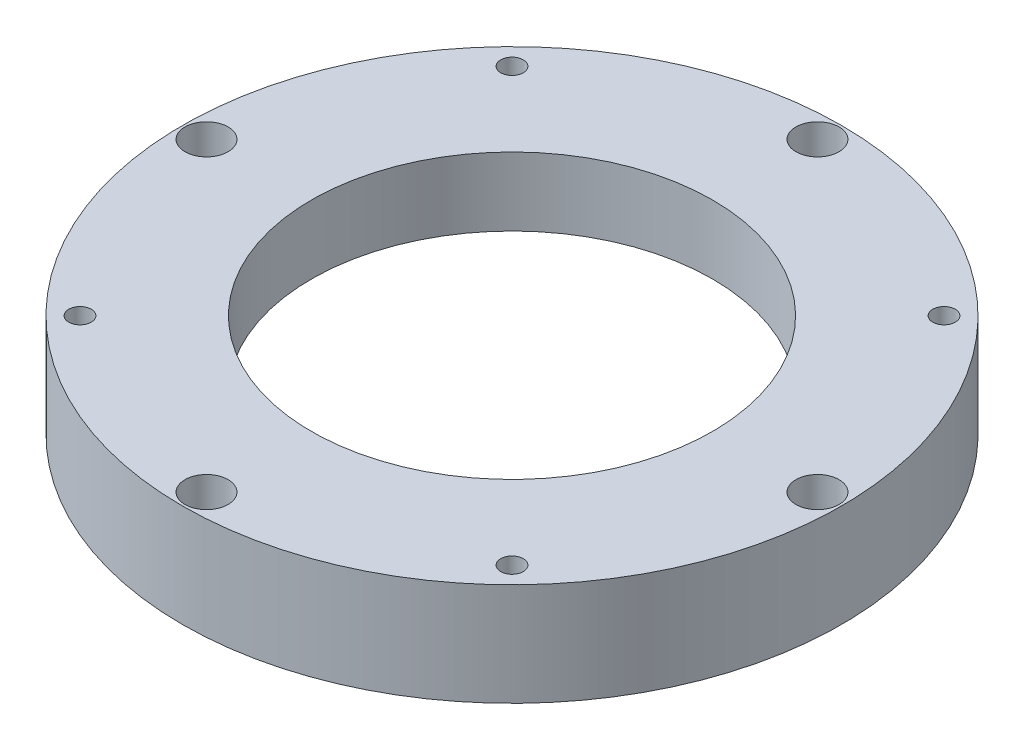
SolidWorks part; units mm, degrees
ref_plane "Front Plane" through (0, 0, 0) normal (0, 0, 1) x (1, 0, 0)
ref_plane "Top Plane" through (0, 0, 0) normal (0, 1, 0) x (1, 0, 0)
ref_plane "Right Plane" through (0, 0, 0) normal (1, 0, 0) x (0, 0, -1)
sketch "Sketch1" plane through (0, 0, 0) normal (0, 1, 0) x (1, 0, 0)
  line L0 (0, 0) -> (42.5, 0) construction
  circle A0 centre (0, 0) radius 45.85
  circle A1 centre (0, 0) radius 27.9
  circle A2 centre (42.5, 0) radius 1.5635
  circle A3 centre (30.052, -30.052) radius 1.5635
  circle A4 centre (0, -42.5) radius 1.5635
  circle A5 centre (0, 0) radius 40
  circle A6 centre (-30.052, -30.052) radius 1.5635
  circle A7 centre (-42.5, 0) radius 1.5635
  circle A8 centre (-30.052, 30.052) radius 1.5635
  circle A9 centre (0, 42.5) radius 1.5635
  circle A10 centre (30.052, 30.052) radius 1.5635
  point P13 (0, 0)
  dimension "D1" = 91.7
  dimension "D2" = 55.8
  dimension "D4" = 3.127
  dimension "D6" = 80
  dimension "D3" = 42.5
  dimension "D5" = 8
extrude "Boss-Extrude1" add sketch "Sketch1" against normal blind 4.7625 contours A0 A5 A2 A4 A3 region at (-44.5532, 0, 0)
extrude "Boss-Extrude2" add sketch "Sketch1<4>" along normal blind 4.7625 contours A1 A5 | A0 A5 A2 A4 A3 region at (-44.5532, 0, 0) region at (-38.8686, 0, 0)
sketch "Sketch1<4>" plane through (0, 0, 0) normal (0, 1, 0) x (1, 0, 0) same geometry as "Sketch1"
sketch "Sketch4" plane through (0, 4.7625, 0) normal (0, 1, 0) x (1, 0, 0)
  line L0 (28.4932, -27.352) -> (26.9343, -30.052)
  line L7 (30.052, 33.1697) -> (27.352, 31.6109)
  line L8 (27.352, 31.6109) -> (27.352, 28.4932)
  line L9 (27.352, 28.4932) -> (30.052, 26.9343)
  line L10 (30.052, 26.9343) -> (32.752, 28.4932)
  line L11 (32.752, 28.4932) -> (32.752, 31.6109)
  line L12 (32.752, 31.6109) -> (30.052, 33.1697)
  line L13 (31.6109, -27.352) -> (28.4932, -27.352)
  line L14 (33.1697, -30.052) -> (31.6109, -27.352)
  line L15 (31.6109, -32.752) -> (33.1697, -30.052)
  line L16 (28.4932, -32.752) -> (31.6109, -32.752)
  line L17 (26.9343, -30.052) -> (28.4932, -32.752)
  line L18 (-27.352, -28.4932) -> (-30.052, -26.9343)
  line L19 (-27.352, -31.6109) -> (-27.352, -28.4932)
  line L20 (-30.052, -33.1697) -> (-27.352, -31.6109)
  line L21 (-32.752, -31.6109) -> (-30.052, -33.1697)
  line L22 (-32.752, -28.4932) -> (-32.752, -31.6109)
  line L23 (-30.052, -26.9343) -> (-32.752, -28.4932)
  line L24 (-28.4932, 27.352) -> (-26.9343, 30.052)
  line L25 (-31.6109, 27.352) -> (-28.4932, 27.352)
  line L26 (-33.1697, 30.052) -> (-31.6109, 27.352)
  line L27 (-31.6109, 32.752) -> (-33.1697, 30.052)
  line L28 (-28.4932, 32.752) -> (-31.6109, 32.752)
  line L29 (-26.9343, 30.052) -> (-28.4932, 32.752)
  circle A0 centre (30.052, 30.052) radius 2.7 construction
  point P1 (31.402, 32.3903)
  point P32 (0, 0)
  dimension "D1" = 5.4
  dimension "D2" = 4
extrude "Cut-Extrude2" cut sketch "Sketch4" against normal blind 4.7625
sketch "Sketch3" plane through (0, 4.7625, 0) normal (0, 1, 0) x (1, 0, 0)
  circle A6 centre (0, -42.5) radius 1.5635 construction
  circle A7 centre (42.5, 0) radius 1.5635 construction
  circle A8 centre (0, 42.5) radius 1.5635 construction
  circle A9 centre (-42.5, 0) radius 1.5635 construction
  circle A10 centre (0, 0) radius 27.9 construction
  circle A11 centre (0, 0) radius 45.85 construction
  circle A12 centre (0, -42.5) radius 1.5635
  circle A13 centre (42.5, 0) radius 1.5635
  circle A14 centre (0, 42.5) radius 1.5635
  circle A15 centre (-42.5, 0) radius 1.5635
  circle A16 centre (0, 0) radius 27.9
  circle A17 centre (0, 0) radius 45.85
  circle A18 centre (0, 42.5) radius 3
  circle A19 centre (42.5, 0) radius 3
  circle A20 centre (0, -42.5) radius 3
  circle A21 centre (-42.5, 0) radius 3
  circle A22 centre (-30.052, 30.052) radius 1.565
  circle A23 centre (30.052, 30.052) radius 1.565
  circle A24 centre (30.052, -30.052) radius 1.565
  circle A25 centre (-30.052, -30.052) radius 1.565
  circle M1 centre (0, 0) radius 27.9
  circle M6 centre (0, 0) radius 45.85
  line M21 (-33.1697, 30.052) -> (-31.6109, 32.752)
  line M22 (-31.6109, 32.752) -> (-28.4932, 32.752)
  line M23 (-28.4932, 32.752) -> (-26.9343, 30.052)
  line M24 (-26.9343, 30.052) -> (-28.4932, 27.352)
  line M25 (-28.4932, 27.352) -> (-31.6109, 27.352)
  line M26 (-31.6109, 27.352) -> (-33.1697, 30.052)
  line M27 (-30.052, -33.1697) -> (-32.752, -31.6109)
  line M28 (-32.752, -31.6109) -> (-32.752, -28.4932)
  line M29 (-32.752, -28.4932) -> (-30.052, -26.9343)
  line M30 (-30.052, -26.9343) -> (-27.352, -28.4932)
  line M31 (-27.352, -28.4932) -> (-27.352, -31.6109)
  line M32 (-27.352, -31.6109) -> (-30.052, -33.1697)
  line M33 (33.1697, -30.052) -> (31.6109, -32.752)
  line M34 (31.6109, -32.752) -> (28.4932, -32.752)
  line M35 (28.4932, -32.752) -> (26.9343, -30.052)
  line M36 (26.9343, -30.052) -> (28.4932, -27.352)
  line M37 (28.4932, -27.352) -> (31.6109, -27.352)
  line M38 (31.6109, -27.352) -> (33.1697, -30.052)
  line M39 (30.052, 33.1697) -> (32.752, 31.6109)
  line M40 (32.752, 31.6109) -> (32.752, 28.4932)
  line M41 (32.752, 28.4932) -> (30.052, 26.9343)
  line M42 (30.052, 26.9343) -> (27.352, 28.4932)
  line M43 (27.352, 28.4932) -> (27.352, 31.6109)
  line M44 (27.352, 31.6109) -> (30.052, 33.1697)
  dimension "D1" = 6
  dimension "D2" = 3.13
extrude "Boss-Extrude3" add sketch "Sketch3" along normal blind 4.7625 contours A21 A20 A19 A18 M6 M1 M44 M39 M40 M41 M42 M43 M38 M33 M34 M35 M36 M37 M32 M27 M28 M29 M30 M31 M26 M21 M22 M23 M24 M25 | A22 M21 M26 M25 M24 M23 M22 | A23 M39 M44 M43 M42 M41 M40 | A24 M33 M38 M37 M36 M35 M34 | A25 M27 M32 M31 M30 M29 M28 region at (-45.7203, 4.7625, 0) region at (-32.3189, 4.7625, -31.3608) region at (-31.3608, 4.7625, 32.3189) region at (32.3189, 4.7625, 31.3608) region at (31.3608, 4.7625, -32.3189)
sketch "Sketch5" plane through (0, 9.525, 0) normal (0, 1, 0) x (1, 0, 0)
  line L0 (0, 0) -> (30.052, 30.052) construction
  circle A0 centre (0, 42.5) radius 3 construction
  circle A1 centre (30.052, 30.052) radius 1.565 construction
  circle A2 centre (42.5, 0) radius 3 construction
  circle A3 centre (30.052, -30.052) radius 1.565 construction
  circle A4 centre (0, -42.5) radius 3 construction
  circle A5 centre (-30.052, -30.052) radius 1.565 construction
  circle A6 centre (-42.5, 0) radius 3 construction
  circle A7 centre (-30.052, 30.052) radius 1.565 construction
  circle A8 centre (0, 0) radius 45.85 construction
  circle A9 centre (0, 0) radius 27.9 construction
  circle A10 centre (0, 42.5) radius 3
  circle A11 centre (30.052, 30.052) radius 1.565
  circle A12 centre (42.5, 0) radius 3
  circle A13 centre (30.052, -30.052) radius 1.565
  circle A14 centre (0, -42.5) radius 3
  circle A15 centre (-30.052, -30.052) radius 1.565
  circle A16 centre (-42.5, 0) radius 3
  circle A17 centre (-30.052, 30.052) radius 1.565
  circle A18 centre (0, 0) radius 45.85
  circle A19 centre (0, 0) radius 27.9
  arc A20 (6.31, 31.2697) -> (18.4511, 26.0224) centre (0, 0) cw
  arc A21 (4.6718, 37.2871) -> (6.4423, 39.762) centre (0, 42.5) ccw
  arc A22 (24.5734, 31.0284) -> (24.5119, 29.527) centre (30.052, 30.052) ccw
  arc A23 (24.5119, 29.527) -> (18.4511, 26.0224) centre (20.6784, 29.1636) cw
  arc A24 (4.6718, 37.2871) -> (6.31, 31.2697) centre (7, 34.6892) ccw
  arc A25 (22.8162, 35.0834) -> (24.5734, 31.0284) centre (20.6354, 31.7302) cw
  arc A26 (8.6987, 40.936) -> (6.4423, 39.762) centre (8.283, 38.9797) ccw
  arc A27 (22.8162, 35.0834) -> (8.6987, 40.936) centre (0, 0) ccw
  arc A28 (35.0834, 22.8162) -> (31.0284, 24.5734) centre (31.7302, 20.6354) ccw
  arc A29 (31.0284, 24.5734) -> (29.527, 24.5119) centre (30.052, 30.052) cw
  arc A30 (29.527, 24.5119) -> (26.0224, 18.4511) centre (29.1636, 20.6784) ccw
  arc A31 (31.2697, 6.31) -> (26.0224, 18.4511) centre (0, 0) ccw
  arc A32 (35.0834, 22.8162) -> (40.936, 8.6987) centre (0, 0) cw
  arc A33 (40.936, 8.6987) -> (39.762, 6.4423) centre (38.9797, 8.283) cw
  arc A34 (37.2871, 4.6718) -> (39.762, 6.4423) centre (42.5, 0) cw
  arc A35 (37.2871, 4.6718) -> (31.2697, 6.31) centre (34.6892, 7) cw
  arc A36 (37.2871, -4.6718) -> (31.2697, -6.31) centre (34.6892, -7) ccw
  arc A37 (31.2697, -6.31) -> (26.0224, -18.4511) centre (0, 0) cw
  arc A38 (29.527, -24.5119) -> (26.0224, -18.4511) centre (29.1636, -20.6784) cw
  arc A39 (31.0284, -24.5734) -> (29.527, -24.5119) centre (30.052, -30.052) ccw
  arc A40 (35.0834, -22.8162) -> (31.0284, -24.5734) centre (31.7302, -20.6354) cw
  arc A41 (35.0834, -22.8162) -> (40.936, -8.6987) centre (0, 0) ccw
  arc A42 (40.936, -8.6987) -> (39.762, -6.4423) centre (38.9797, -8.283) ccw
  arc A43 (37.2871, -4.6718) -> (39.762, -6.4423) centre (42.5, 0) ccw
  arc A44 (24.5119, -29.527) -> (18.4511, -26.0224) centre (20.6784, -29.1636) ccw
  arc A45 (24.5734, -31.0284) -> (24.5119, -29.527) centre (30.052, -30.052) cw
  arc A46 (22.8162, -35.0834) -> (24.5734, -31.0284) centre (20.6354, -31.7302) ccw
  arc A47 (22.8162, -35.0834) -> (8.6987, -40.936) centre (0, 0) cw
  arc A48 (6.31, -31.2697) -> (18.4511, -26.0224) centre (0, 0) ccw
  arc A49 (4.6718, -37.2871) -> (6.31, -31.2697) centre (7, -34.6892) cw
  arc A50 (4.6718, -37.2871) -> (6.4423, -39.762) centre (0, -42.5) cw
  arc A51 (8.6987, -40.936) -> (6.4423, -39.762) centre (8.283, -38.9797) cw
  arc A52 (-4.6718, -37.2871) -> (-6.31, -31.2697) centre (-7, -34.6892) ccw
  arc A53 (-6.31, -31.2697) -> (-18.4511, -26.0224) centre (0, 0) cw
  arc A54 (-24.5119, -29.527) -> (-18.4511, -26.0224) centre (-20.6784, -29.1636) cw
  arc A55 (-24.5734, -31.0284) -> (-24.5119, -29.527) centre (-30.052, -30.052) ccw
  arc A56 (-22.8162, -35.0834) -> (-24.5734, -31.0284) centre (-20.6354, -31.7302) cw
  arc A57 (-22.8162, -35.0834) -> (-8.6987, -40.936) centre (0, 0) ccw
  arc A58 (-8.6987, -40.936) -> (-6.4423, -39.762) centre (-8.283, -38.9797) ccw
  arc A59 (-4.6718, -37.2871) -> (-6.4423, -39.762) centre (0, -42.5) ccw
  arc A60 (-29.527, -24.5119) -> (-26.0224, -18.4511) centre (-29.1636, -20.6784) ccw
  arc A61 (-31.0284, -24.5734) -> (-29.527, -24.5119) centre (-30.052, -30.052) cw
  arc A62 (-35.0834, -22.8162) -> (-31.0284, -24.5734) centre (-31.7302, -20.6354) ccw
  arc A63 (-35.0834, -22.8162) -> (-40.936, -8.6987) centre (0, 0) cw
  arc A64 (-31.2697, -6.31) -> (-26.0224, -18.4511) centre (0, 0) ccw
  arc A65 (-37.2871, -4.6718) -> (-31.2697, -6.31) centre (-34.6892, -7) cw
  arc A66 (-37.2871, -4.6718) -> (-39.762, -6.4423) centre (-42.5, 0) cw
  arc A67 (-40.936, -8.6987) -> (-39.762, -6.4423) centre (-38.9797, -8.283) cw
  arc A68 (-37.2871, 4.6718) -> (-31.2697, 6.31) centre (-34.6892, 7) ccw
  arc A69 (-31.2697, 6.31) -> (-26.0224, 18.4511) centre (0, 0) cw
  arc A70 (-29.527, 24.5119) -> (-26.0224, 18.4511) centre (-29.1636, 20.6784) cw
  arc A71 (-31.0284, 24.5734) -> (-29.527, 24.5119) centre (-30.052, 30.052) ccw
  arc A72 (-35.0834, 22.8162) -> (-31.0284, 24.5734) centre (-31.7302, 20.6354) cw
  arc A73 (-35.0834, 22.8162) -> (-40.936, 8.6987) centre (0, 0) ccw
  arc A74 (-40.936, 8.6987) -> (-39.762, 6.4423) centre (-38.9797, 8.283) ccw
  arc A75 (-37.2871, 4.6718) -> (-39.762, 6.4423) centre (-42.5, 0) ccw
  arc A76 (-24.5119, 29.527) -> (-18.4511, 26.0224) centre (-20.6784, 29.1636) ccw
  arc A77 (-24.5734, 31.0284) -> (-24.5119, 29.527) centre (-30.052, 30.052) cw
  arc A78 (-22.8162, 35.0834) -> (-24.5734, 31.0284) centre (-20.6354, 31.7302) ccw
  arc A79 (-22.8162, 35.0834) -> (-8.6987, 40.936) centre (0, 0) cw
  arc A80 (-6.31, 31.2697) -> (-18.4511, 26.0224) centre (0, 0) ccw
  arc A81 (-4.6718, 37.2871) -> (-6.31, 31.2697) centre (-7, 34.6892) cw
  arc A82 (-4.6718, 37.2871) -> (-6.4423, 39.762) centre (0, 42.5) cw
  arc A83 (-8.6987, 40.936) -> (-6.4423, 39.762) centre (-8.283, 38.9797) cw
  point P137 (0, 0)
  dimension "D1" = 4
  dimension "D2" = 4
  dimension "D3" = 4
  dimension "D4" = 4
  dimension "D5" = 12
  dimension "D8" = 2
  dimension "D9" = 4
  dimension "D7" = 14
  dimension "D6" = 4
extrude "Cut-Extrude3" [suppressed] cut sketch "Sketch5" against normal blind 4.7625 contours A75 A68 A69 A70 A71 A72 A73 A74 | A83 A79 A78 A77 A76 A80 A81 A82 | A25 A27 A26 A21 A24 A20 A23 A22 | A35 A34 A33 A32 A28 A29 A30 A31 | A43 A36 A37 A38 A39 A40 A41 A42 | A51 A47 A46 A45 A44 A48 A49 A50 | A59 A52 A53 A54 A55 A56 A57 A58 | A67 A63 A62 A61 A60 A64 A65 A66
equation "\"bearing_21_OD\"= 21mm"
equation "\"pin_cirlce_diameter\"= 75mm"
equation "\"pin_diam\"= 6mm"
equation "\"gear_thickness\"= 4mm"
equation "\"ball_bearing_diam\"= 3.214mm"
equation "\"bearing_21_outer_clearance\"= 0.127mm'change this"
equation "\"bearing_15_OD\"= 15mm"
equation "\"bearing_15_outer_clearance\"= 0mm'change this"
equation "\"thrust_bearing_thickness\"= 5mm'measure this irl and change"
equation "\"D1@Boss-Extrude1\"=\"sheetThickness\""
equation "\"largeBearOD\"= 21mm"
equation "\"largeBearID\" = 15mm"
equation "\"largeBearOTight\"= 0.34375mm'calibrate - hold onto gears"
equation "\"largeBearITight\"= 0mm'calibrate - hold onto eccentric nut"
equation "\"largeBearFlangeDiam\" = 22.5mm"
equation "\"largeBearFlangeWidth\" = 0.8mm"
equation "\"smallBearOD\"= 15mm"
equation "\"smallBearOTight\"= 0.2mm'calibrate - hold onto bottom of gearbox"
equation "\"smallBearOLoose\"= 0mm'calibrate - able to take off topHat"
equation "\"smallBearID\" = 10mm"
equation "\"smallBearITight\" = 0mm'hold onto "
equation "\"pinCircleDiam\"= 75mm"
equation "\"pinDiam\"= 6mm"
equation "\"sheetThickness\"= 0.1875in"
equation "\"ballBearDiam\"= 3.5mm"
equation "\"thrustBearingThickness\"= 5mm'measure this irl and change"
equation "\"thrustBearingID\"= 0mm'measure this irl and change"
equation "\"thrustBearingOD\"= 0mm'measure this irl and change"
equation "\"eccentricity\" = 1mm"
equation "\"D1@Boss-Extrude2\"=\"sheetThickness\""
equation "\"D1@Boss-Extrude3\"=\"sheetThickness\""
equation "\"D1@Cut-Extrude2\"=\"sheetThickness\""
equation "\"D1@Cut-Extrude3\"=\"sheetThickness\""
